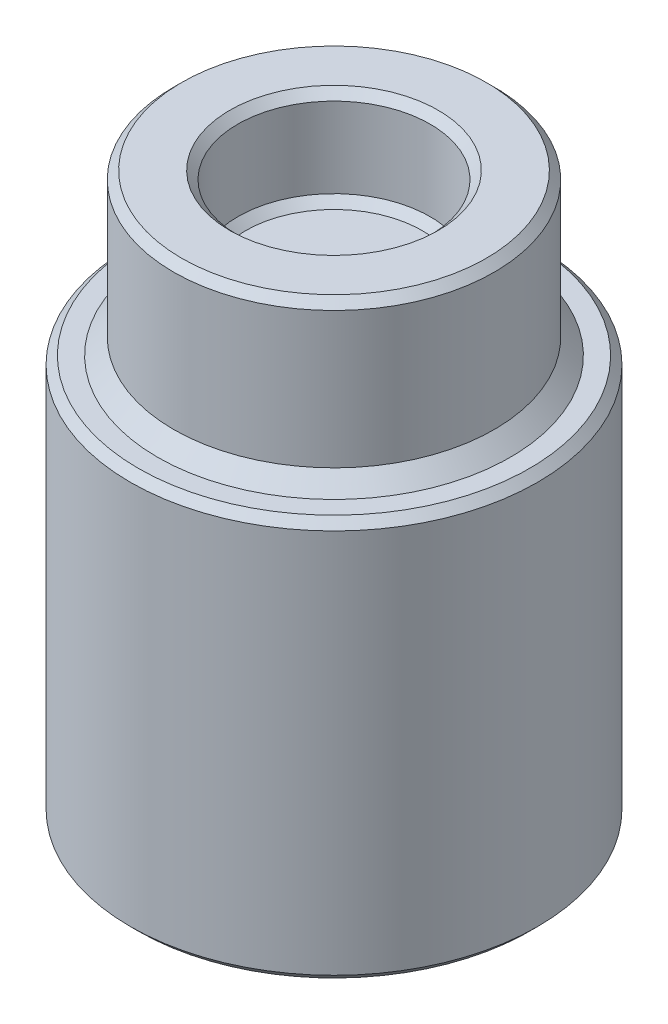
SolidWorks part; units mm, degrees
note: '?' marks a value the reader was unsure of. The reader was unsure of these and kept them because the rebuilt part matched: shared geometry of "Sketch1<3>".
material "ABS"
ref_plane "Front Plane" through (0, 0, 0) normal (0, 0, 1) x (1, 0, 0)
ref_plane "Top Plane" through (0, 0, 0) normal (0, 1, 0) x (1, 0, 0)
ref_plane "Right Plane" through (0, 0, 0) normal (1, 0, 0) x (0, 0, -1)
ref_axis "X Axis" through (88.99, 0, 0) along (-1, 0, 0)?
ref_axis "Y Axis" through (0, 55, 0) along (0, -1, 0)?
ref_axis "Z Axis" through (0, 0, -88.99) along (0, 0, 1)?
sketch "Sketch1" plane through (0, 0, 0) normal (0, 1, 0) x (1, 0, 0)
  circle A0 centre (0, 0) radius 5
  circle A1 centre (0, 0) radius 3
  dimension "D1" = 6
  dimension "D2" = 10
extrude "Boss-Extrude1" add sketch "Sketch1" along normal blind 2 contours A1 | A0 A1
extrude "Boss-Extrude2" add sketch "Sketch1<3>" along normal blind 5
sketch "Sketch1<3>" plane through (0, 0, 0) normal (0, 1, 0) x (1, 0, 0) same geometry as "Sketch1"
chamfer "Chamfer1" distance 0.25 angle 45 3 edges at (0, 5, 3) (0, 5, 5) (0, 2, 3)
sketch "Sketch5" plane through (0, 0, 0) normal (0, 1, 0) x (1, 0, 0)
  circle A0 centre (0, 0) radius 6.35
  dimension "D1" = 12.7
extrude "Boss-Extrude4" add sketch "Sketch5" against normal blind 12.5
sketch "Sketch4" plane through (0, -12.5, 0) normal (0, -1, 0) x (-1, 0, 0)
  point P0 (0, 0)
hole_wizard "3/8 (0.375) Diameter Hole1" positions "Sketch4" profile "Sketch3" hole size "3/8" standard "ANSI Inch"
sketch "Sketch3" plane through (0, -12.5, 0) normal (1, 0, 0) x (0, 0, -1)
  line L0 (0, 0) -> (0, 12.5)
  line L1 (0, 12.5) -> (4.7625, 12.0833)
  line L2 (4.7625, 12.0833) -> (4.7625, 0.635)
  line L3 (4.7625, 0.635) -> (5.3975, 0)
  line L5 (5.3975, 0) -> (0, 0)
  line L6 (-4.7625, 0.635) -> (-5.3975, 0) construction
  line L10 (0, 12.5) -> (-4.7625, 12.0833) construction
  line L11 (0, -6.35) -> (0, 107.95) construction
  dimension "Hole Dia." = 9.525
  dimension "Hole Depth" = 12.5
  dimension "Near C'Sink Dia." = 10.795
  dimension "Near C'Sink Angle" = 90
  dimension "Drill Angle" = 170
sketch "Sketch8" [suppressed] plane through (0, -4.7625, 0) normal (0, -1, 0) x (-1, 0, 0)
  point P0 (0, 0)
hole_wizard "#2 (0.221) Diameter Hole1" [suppressed] positions "Sketch8" profile "Sketch7" hole size "#2" standard "ANSI Inch"
sketch "Sketch7" plane through (0, -4.7625, 0) normal (1, 0, 0) x (0, 0, -1)
  line L0 (0, 0) -> (0, 4.76)
  line L1 (0, 4.76) -> (2.8067, 4.2651)
  line L2 (2.8067, 4.2651) -> (2.8067, 0.635)
  line L3 (2.8067, 0.635) -> (3.4417, 0)
  line L5 (3.4417, 0) -> (0, 0)
  line L6 (-2.8067, 0.635) -> (-3.4417, 0) construction
  line L10 (0, 4.76) -> (-2.8067, 4.2651) construction
  line L11 (0, -6.35) -> (0, 107.95) construction
  dimension "Hole Dia." = 5.6134
  dimension "Hole Depth" = 4.76
  dimension "Near C'Sink Dia." = 6.8834
  dimension "Near C'Sink Angle" = 90
  dimension "Drill Angle" = 160
sketch "Sketch11" [suppressed] plane through (0, -4.7625, 0) normal (0, -1, 0) x (-1, 0, 0)
  point P0 (0, 0)
hole_wizard "5/16 (0.3125) Diameter Hole1" [suppressed] positions "Sketch11" profile "Sketch10" hole size "5/16" standard "ANSI Inch"
sketch "Sketch10" plane through (0, -4.7625, 0) normal (1, 0, 0) x (0, 0, -1)
  line L0 (0, 0) -> (0, 4.7625)
  line L1 (0, 4.7625) -> (3.9687, 4.4153)
  line L2 (3.9687, 4.4153) -> (3.9688, 0.127)
  line L3 (3.9688, 0.127) -> (4.0957, 0)
  line L5 (4.0957, 0) -> (0, 0)
  line L6 (-3.9688, 0.127) -> (-4.0957, 0) construction
  line L10 (0, 4.7625) -> (-3.9688, 4.4153) construction
  line L11 (0, -6.35) -> (0, 107.95) construction
  dimension "Hole Dia." = 7.9375
  dimension "Hole Depth" = 4.7625
  dimension "Near C'Sink Dia." = 8.1915
  dimension "Near C'Sink Angle" = 90
  dimension "Drill Angle" = 170
chamfer "Chamfer2" distance 0.25 angle 45 2 edges at (0, -12.5, 6.35) (0, 0, 6.35)
chamfer "Chamfer3" distance 0.5 angle 45 1 edges at (0, 0, 5)
